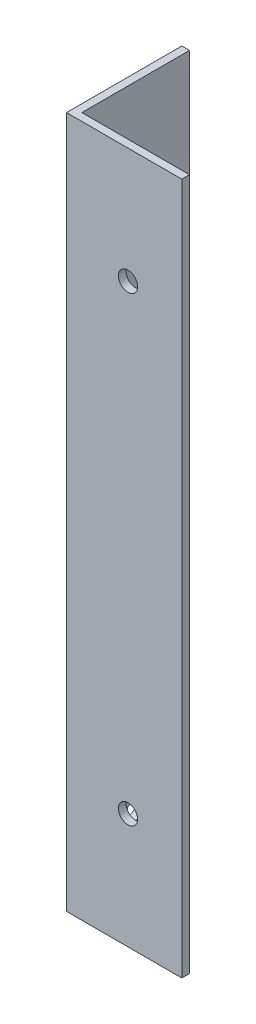
SolidWorks part; units mm, degrees
ref_plane "正面" through (0, 0, 0) normal (0, 0, 1) x (1, 0, 0)
ref_plane "平面" through (0, 0, 0) normal (0, 1, 0) x (1, 0, 0)
ref_plane "右側面" through (0, 0, 0) normal (1, 0, 0) x (0, 0, -1)
sketch "ｽｹｯﾁ1" plane through (0, 0, 0) normal (0, 1, 0) x (1, 0, 0)
  line L1 (0, 0) -> (15, 0)
  line L2 (0, 0) -> (0, -1)
  line L3 (0, -1) -> (15, -1)
  line L4 (15, 0) -> (15, -1)
  dimension "D1" = 15
  dimension "D2" = 1
sketch "ｽｹｯﾁ2" plane through (0, 0, 0) normal (0, 1, 0) x (1, 0, 0)
extrude "ﾎﾞｽ - 押し出し1" add sketch "ｽｹｯﾁ1" along normal blind 90
sketch "ｽｹｯﾁ3" plane through (0, 0, 0) normal (0, 0, -1) x (-1, 0, 0)
  line L1 (0, 90) -> (-1, 90)
  line L2 (0, 90) -> (0, 0)
  line L3 (0, 0) -> (-1, 0)
  line L4 (-1, 90) -> (-1, 0)
  dimension "D1" = 1
  dimension "D2" = 90
extrude "ﾎﾞｽ - 押し出し2" add sketch "ｽｹｯﾁ3" along normal blind 14
hole_wizard "M3x0.5 ねじ穴1" positions "ｽｹｯﾁ4" profile "ｽｹｯﾁ5" tap size "M3x0.5" standard "JIS" end condition through all
sketch "ｽｹｯﾁ4" plane through (0, 0, 1) normal (0, 0, 1) x (1, 0, 0)
  line L0 (8.25, 0) -> (-8.25, 0) construction
  line L1 (0, 90) -> (0, 0) construction
  point P0 (8, 15)
  point P2 (8, 75)
  dimension "D1" = 15
  dimension "D2" = 60
  dimension "D3" = 8
  dimension "D4" = 8
sketch "ｽｹｯﾁ5" plane through (8, 15, 1) normal (1, 0, 0) x (0, -1, 0)
  line L0 (0, 0) -> (0, 15)
  line L1 (0, 15) -> (1.25, 15)
  line L2 (1.25, 15) -> (1.25, 0)
  line L5 (1.25, 0) -> (0, 0)
  line L11 (0, -6.35) -> (0, 107.95) construction
  dimension "次ｻｰﾌｪｽまでのねじ下穴ﾄﾞﾘﾙ直径" = 2.5
  dimension "次ｻｰﾌｪｽまでのねじ下穴ﾄﾞﾘﾙの深さ" = 15
cosmetic thread "穴のねじ山1" parameters "D2"=3
cosmetic thread "穴のねじ山2" parameters "D2"=3
hole_wizard "M3x0.5 ねじ穴2" positions "ｽｹｯﾁ6" profile "ｽｹｯﾁ7" tap size "M3x0.5" standard "JIS" end condition through all
sketch "ｽｹｯﾁ6" plane through (0, 0, 0) normal (-1, 0, 0) x (0, 0, 1)
  line L0 (-14, 0) -> (-14, 90) construction
  line L1 (8.25, 0) -> (-8.25, 0) construction
  point P0 (-7, 8)
  dimension "D1" = 7
  dimension "D2" = 8
sketch "ｽｹｯﾁ7" plane through (0, 8, -7) normal (0, 1, 0) x (0, 0, 1)
  line L0 (0, 0) -> (0, 15)
  line L1 (0, 15) -> (1.25, 15)
  line L2 (1.25, 15) -> (1.25, 0)
  line L5 (1.25, 0) -> (0, 0)
  line L11 (0, -6.35) -> (0, 107.95) construction
  dimension "次ｻｰﾌｪｽまでのねじ下穴ﾄﾞﾘﾙ直径" = 2.5
  dimension "次ｻｰﾌｪｽまでのねじ下穴ﾄﾞﾘﾙの深さ" = 15
cosmetic thread "穴のねじ山3" parameters "D2"=3
